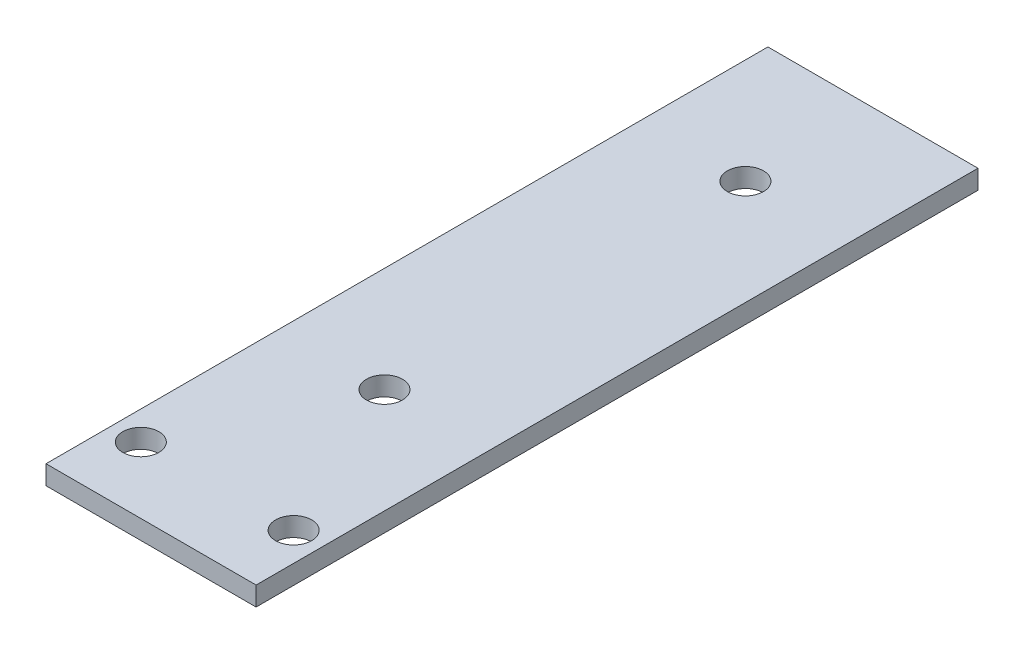
SolidWorks part; units mm, degrees
ref_plane "Front Plane" through (0, 0, 0) normal (0, 0, 1) x (1, 0, 0)
ref_plane "Top Plane" through (0, 0, 0) normal (0, 1, 0) x (1, 0, 0)
ref_plane "Right Plane" through (0, 0, 0) normal (1, 0, 0) x (0, 0, -1)
ref_plane "Plane1" through (0, -34.925, 0) normal (0, -1, 0) x (1, 0, 0)
sketch "Sketch1" plane through (0, -34.925, 0) normal (0, -1, 0) x (1, 0, 0)
  line L0 (-3.175, -115) -> (34.925, -115)
  line L1 (34.925, -115) -> (34.925, 5)
  line L2 (34.925, 5) -> (-3.175, 5)
  line L3 (-3.175, 5) -> (-3.175, -115)
extrude "Boss-Extrude1" add sketch "Sketch1" against normal blind 38.1
sketch "Sketch2" plane through (0, 0, -115) normal (0, 0, -1) x (-1, 0, 0)
  line L0 (-34.925, -34.925) -> (0, -34.925)
  line L1 (0, -34.925) -> (0, 0)
  line L2 (0, 0) -> (-34.925, 0)
  line L3 (-34.925, 0) -> (-34.925, -34.925)
extrude "Cut-Extrude1" cut sketch "Sketch2" against normal through all
sketch "Sketch18" plane through (0, 0, 5) normal (0, 0, 1) x (1, 0, 0)
  line L1 (-3.175, 3.175) -> (0, 3.175)
  line L2 (-3.175, 3.175) -> (-3.175, 0)
  line L3 (-3.175, 0) -> (0, 0)
  line L4 (0, 3.175) -> (0, 0)
extrude "Cut-Extrude3" cut sketch "Sketch18" against normal through all
sketch "Sketch19" plane through (0, 0, 0) normal (0, -1, 0) x (1, 0, 0)
  line L0 (17.4625, 5) -> (17.4625, -115) construction
  line L1 (0, 5) -> (34.925, 5) construction
  line L2 (0, -115) -> (34.925, -115) construction
  line L3 (17.4625, -6) -> (0, -6) construction
  line L4 (0, 5) -> (0, -115) construction
  line L5 (17.4625, -6) -> (34.925, -6) construction
  line L6 (34.925, 5) -> (34.925, -115) construction
  circle A0 centre (17.4625, -93.8) radius 3
  circle A1 centre (17.4625, -33.8) radius 3
  circle A3 centre (4.7625, -6) radius 3
  circle A4 centre (30.1625, -6) radius 3
  dimension "D1" = 6
  dimension "D2" = 6
  dimension "D3" = 12.7
  dimension "D4" = 21.2
  dimension "D6" = 12.7
  dimension "D5" = 81.2
  dimension "D7" = 6
  dimension "D8" = 6
  dimension "D9" = 109
extrude "Cut-Extrude4" cut sketch "Sketch19" against normal through all
